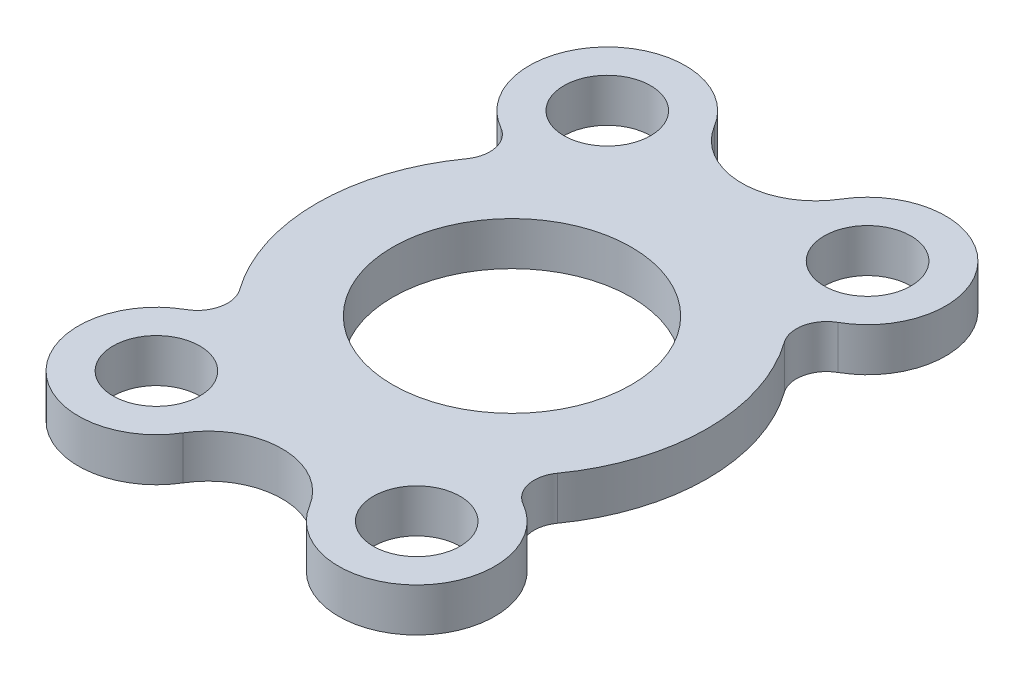
SolidWorks part; units mm, degrees
ref_plane "Спереди" through (0, 0, 0) normal (0, 0, 1) x (1, 0, 0)
ref_plane "Сверху" through (0, 0, 0) normal (0, 1, 0) x (1, 0, 0)
ref_plane "Справа" through (0, 0, 0) normal (1, 0, 0) x (0, 0, -1)
sketch "Эскиз1" plane through (0, 0, 0) normal (0, 1, 0) x (1, 0, 0)
  line L0 (0, -116.5186) -> (0, 116.5186) construction
  line L1 (-126.7582, 0) -> (126.7582, 0) construction
  line L2 (30, -51.9615) -> (0, 0) construction
  line L3 (30, 51.9615) -> (0, 0) construction
  circle A0 centre (0, 0) radius 27.5
  arc A1 (36.6267, -26.1436) -> (36.6267, 26.1436) centre (0, 0) ccw
  circle A2 centre (30, -51.9615) radius 10
  arc A3 (14.5714, -61.2329) -> (38.8734, -36.3007) centre (30, -51.9615) ccw
  arc A4 (36.6267, -26.1436) -> (38.8734, -36.3007) centre (42.3242, -30.2103) ccw
  arc A5 (-36.6267, -26.1436) -> (-38.8734, -36.3007) centre (-42.3242, -30.2103) cw
  circle A6 centre (-30, -51.9615) radius 10
  arc A7 (-14.5714, -61.2329) -> (-38.8734, -36.3007) centre (-30, -51.9615) cw
  arc A8 (14.5714, -61.2329) -> (-14.5714, -61.2329) centre (0, -69.9893) ccw
  arc A9 (-36.6267, 26.1436) -> (-36.6267, -26.1436) centre (0, 0) ccw
  arc A10 (14.5714, 61.2329) -> (-14.5714, 61.2329) centre (0, 69.9893) cw
  arc A11 (-14.5714, 61.2329) -> (-38.8734, 36.3007) centre (-30, 51.9615) ccw
  circle A12 centre (-30, 51.9615) radius 10
  arc A13 (-36.6267, 26.1436) -> (-38.8734, 36.3007) centre (-42.3242, 30.2103) ccw
  arc A14 (36.6267, 26.1436) -> (38.8734, 36.3007) centre (42.3242, 30.2103) cw
  arc A15 (14.5714, 61.2329) -> (38.8734, 36.3007) centre (30, 51.9615) cw
  circle A16 centre (30, 51.9615) radius 10
  point P10 (0, 0)
  point P13 (0, 0)
  dimension "D1" = 55
  dimension "D2" = 90
  dimension "D4" = 20
  dimension "D5" = 36
  dimension "D7" = 14
  dimension "D8" = 34
  dimension "D3" = 60
  dimension "D6" = 30
extrude "Бобышка-Вытянуть1" add sketch "Эскиз1" along normal blind 10
sketch "Эскиз2" plane through (0, 10, 0) normal (0, 1, 0) x (1, 0, 0)
  arc A0 (-36.6267, 26.1436) -> (-36.6267, -26.1436) centre (0, 0) ccw construction
  circle A1 centre (0, 0) radius 27.5 construction
  arc A2 (-36.6267, 26.1436) -> (-36.6267, -26.1436) centre (0, 0) ccw
  circle A3 centre (0, 0) radius 27.5
  circle A4 centre (0, 0) radius 45
ref_axis "Ось1" through (0, -50, 0) along (0, 1, 0)
